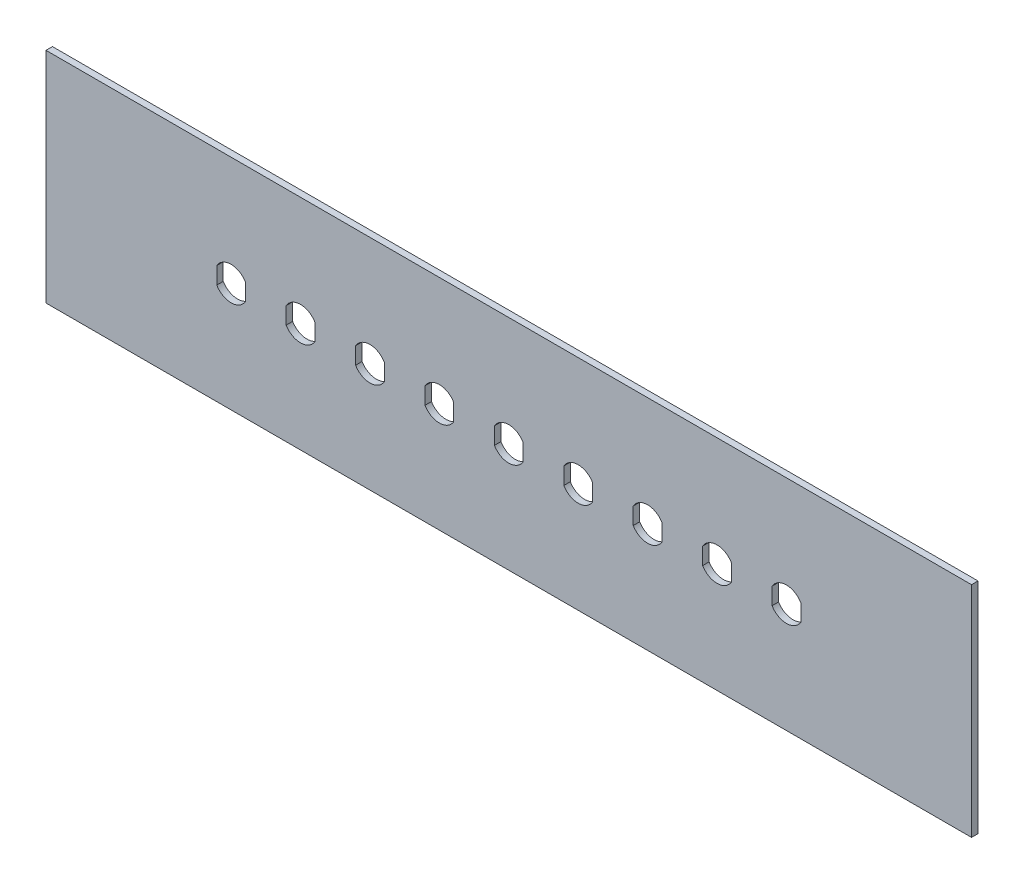
SolidWorks part; units mm, degrees
ref_plane "Front Plane" through (0, 0, 0) normal (0, 0, 1) x (1, 0, 0)
ref_plane "Top Plane" through (0, 0, 0) normal (0, 1, 0) x (1, 0, 0)
ref_plane "Right Plane" through (0, 0, 0) normal (1, 0, 0) x (0, 0, -1)
sketch "Sketch1" plane through (0, 0, 0) normal (0, 0, 1) x (1, 0, 0)
  line L0 (50.8, 30.0355) -> (69.85, 30.0355) construction
  line L1 (0, 60.071) -> (254, 60.071)
  line L2 (0, 60.071) -> (0, 0)
  line L3 (0, 0) -> (254, 0)
  line L4 (254, 60.071) -> (254, 0)
  line L5 (69.85, 30.0355) -> (88.9, 30.0355) construction
  line L6 (88.9, 30.0355) -> (107.95, 30.0355) construction
  line L7 (107.95, 30.0355) -> (127, 30.0355) construction
  line L8 (127, 30.0355) -> (146.05, 30.0355) construction
  line L9 (146.05, 30.0355) -> (165.1, 30.0355) construction
  line L10 (165.1, 30.0355) -> (184.15, 30.0355) construction
  line L11 (184.15, 30.0355) -> (203.2, 30.0355) construction
  line L12 (203.2, 30.0355) -> (254, 30.0355) construction
  line L13 (50.8, 30.0355) -> (0, 30.0355) construction
  line L14 (54.737, 27.711) -> (54.737, 32.36)
  line L15 (46.863, 32.36) -> (46.863, 27.711)
  arc A0 (54.737, 32.36) -> (46.863, 32.36) centre (50.8, 30.0355) ccw
  circle A1 centre (69.85, 30.0355) radius 4.572
  circle A2 centre (88.9, 30.0355) radius 4.572
  circle A3 centre (107.95, 30.0355) radius 4.572
  circle A4 centre (127, 30.0355) radius 4.572
  circle A5 centre (146.05, 30.0355) radius 4.572
  circle A6 centre (165.1, 30.0355) radius 4.572
  circle A7 centre (184.15, 30.0355) radius 4.572
  circle A8 centre (203.2, 30.0355) radius 4.572
  arc A9 (46.863, 27.711) -> (54.737, 27.711) centre (50.8, 30.0355) ccw
  dimension "D3" = 9.144
  dimension "D6" = 7.874
  dimension "D7" = 9.144
  dimension "D1" = 254
  dimension "D2" = 60.071
  dimension "D4" = 30.0355
  dimension "D5" = 19.05
extrude "Boss-Extrude1" add sketch "Sketch1" along normal blind 1.778 contours L4 L1 L2 L3 A8 A7 A6 A5 A4 A3 A2 A1 A0 | A1 | A2 | A3 | A4 | A5 | A6 | A7 | A8 | L15 A9 L14 A0 region at (127, 57.4609, 0) region at (50.8, 30.0355, 0) region at (69.85, 30.0355, 0) region at (88.9, 30.0355, 0) region at (107.95, 30.0355, 0) region at (127, 30.0355, 0) region at (146.05, 30.0355, 0) region at (165.1, 30.0355, 0) region at (184.15, 30.0355, 0) region at (203.2, 30.0355, 0)
extrude "Cut-Extrude2" cut sketch "Sketch1<3>" along normal through all contours L15 A9 L14 A0 region at (50.8, 30.0355, 0)
sketch "Sketch1<3>" plane through (0, 0, 0) normal (0, 0, 1) x (1, 0, 0) same geometry as "Sketch1"
pattern_linear "LPattern1" count 9 spacing 19.05 along (1, 0, 0) of "Cut-Extrude2"
